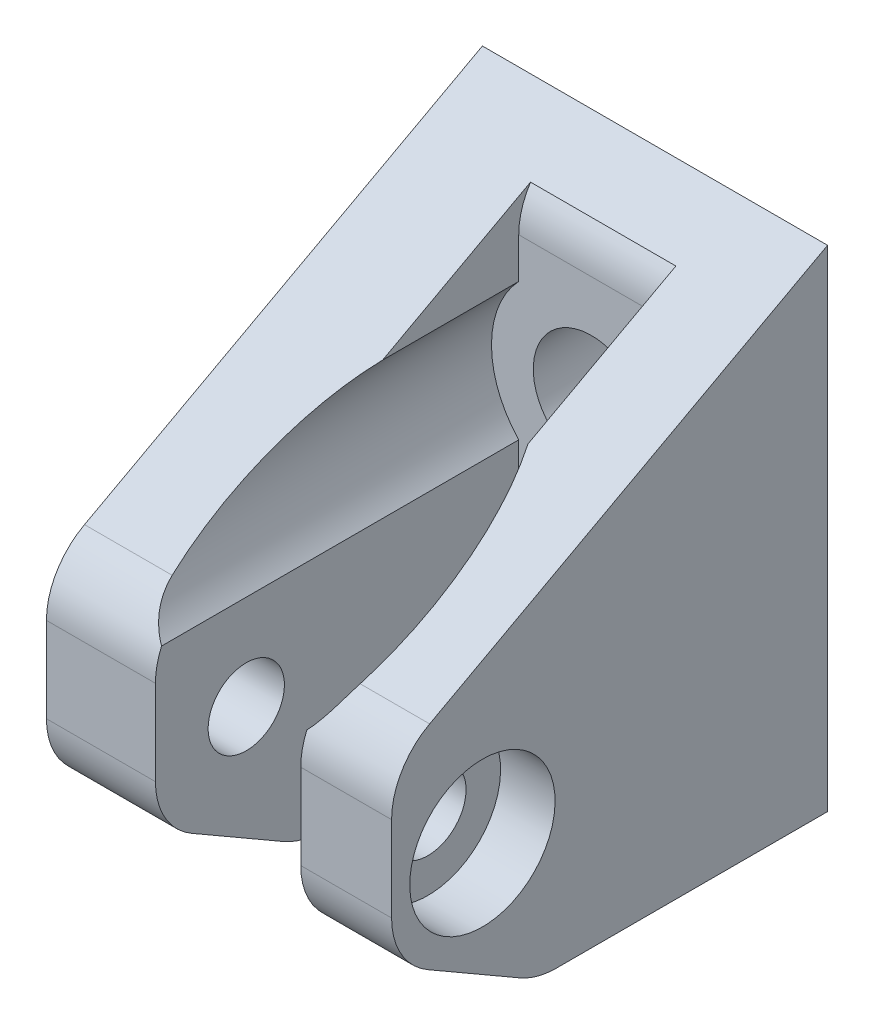
SolidWorks part; units mm, degrees
ref_plane "Plan de face" through (0, 0, 0) normal (0, 0, 1) x (1, 0, 0)
ref_plane "Plan de dessus" through (0, 0, 0) normal (0, 1, 0) x (1, 0, 0)
ref_plane "Plan de droite" through (0, 0, 0) normal (1, 0, 0) x (0, 0, -1)
sketch "Esquisse1" plane through (0, 0, 0) normal (0, 0, 1) x (1, 0, 0)
  line L1 (-10, 17) -> (10, 17)
  line L2 (-10, 17) -> (-10, -17)
  line L3 (-10, -17) -> (10, -17)
  line L4 (10, 17) -> (10, -17)
  dimension "D1" = 34
  dimension "D2" = 10
  dimension "D3" = 20
  dimension "D4" = 17
extrude "Boss.-Extru.1" add sketch "Esquisse1" along normal blind 4
sketch "Esquisse2" plane through (0, 0, 4) normal (0, 0, 1) x (1, 0, 0)
  line L0 (10, 17) -> (-10, 17) construction
  line L1 (-4, 17) -> (4, 17)
  line L2 (-4, 17) -> (-4, 10)
  line L3 (-4, 10) -> (4, 10)
  line L4 (4, 17) -> (4, 10)
  line L5 (10, -17) -> (10, 17) construction
  line L6 (-4, -17) -> (4, -17)
  line L7 (-4, -17) -> (-4, -10)
  line L8 (-4, -10) -> (4, -10)
  line L9 (4, -17) -> (4, -10)
  line L10 (-10, -17) -> (10, -17) construction
  dimension "D1" = 8
  dimension "D2" = 6
  dimension "D3" = 6
  dimension "D4" = 8
  dimension "D5" = 20
extrude "Enlèv. mat.-Extru.1" cut sketch "Esquisse2" against normal through all
fillet "Congé1" radius 4 2 edges at (0, -10, 4) (0, 10, 4)
sketch "Esquisse3" plane through (0, 0, 4) normal (0, 0, 1) x (1, 0, 0)
  line L1 (-10, 17) -> (-4, 17)
  line L2 (-10, 17) -> (-10, -17)
  line L3 (-10, -17) -> (-4, -17)
  line L4 (-4, 17) -> (-4, -17)
  line L5 (4, -17) -> (10, -17)
  line L6 (4, -17) -> (4, 17)
  line L7 (4, 17) -> (10, 17)
  line L8 (10, -17) -> (10, 17)
extrude "Boss.-Extru.2" add sketch "Esquisse3" along normal blind 20
sketch "Esquisse4" plane through (10, 0, 0) normal (1, 0, 0) x (0, 0, -1)
  line L0 (-24, -17) -> (0, -17) construction
  line L3 (-24, -17) -> (-24, 17) construction
  circle A0 centre (-19, 9) radius 2.1
  circle A1 centre (-19, -9) radius 2.1
  dimension "D1" = 4.2
  dimension "D2" = 4.2
  dimension "D3" = 18
  dimension "D4" = 8
  dimension "D5" = 5
  dimension "D6" = 5
extrude "Enlèv. mat.-Extru.2" cut sketch "Esquisse4" against normal through all
chamfer "Chanfrein1" distance 8 angle 30 4 edges at (-7, -17, 24) (7, -17, 24) (-7, 17, 24) (7, 17, 24) first distance on face at (-7, -17, 12) first distance on face at (7, -17, 12) first distance on face at (-7, 17, 12) first distance on face at (7, 17, 12)
fillet "Congé2" radius 4 8 edges at (7, 17, 16) (-7, 17, 16) (-7, 12.3812, 24) (7, 12.3812, 24) (7, -12.3812, 24) (7, -17, 16) (-7, -17, 16) (-7, -12.3812, 24)
sketch "Esquisse5" plane through (0, 0, 4) normal (0, 0, 1) x (1, 0, 0)
  circle A0 centre (0, 0) radius 3.2
  dimension "D1" = 6.4
extrude "Enlèv. mat.-Extru.3" cut sketch "Esquisse5" against normal through all
sketch "Esquisse6" plane through (0, 0, 4) normal (0, 0, 1) x (1, 0, 0)
  circle A0 centre (0, 0) radius 5.5
  dimension "D1" = 11
extrude "Enlèv. mat.-Extru.4" cut sketch "Esquisse6" along normal through all
sketch "Esquisse8" plane through (10, 0, 0) normal (1, 0, 0) x (0, 0, -1)
  line L0 (0, 17) -> (0, 10)
  line L1 (0, -17) -> (0, 17) construction
  line L2 (0, 10) -> (-24, -3)
  line L3 (-24, -10.0718) -> (-24, 10.0718) construction
  line L4 (-24, -3) -> (-24, 17)
  line L5 (-24, 17) -> (0, 17)
  dimension "D1" = 20
extrude "Enlèv. mat.-Extru.5" cut sketch "Esquisse8" against normal through all
fillet "Congé3" radius 4 2 edges at (7.3049, -3, 24) (-7.3049, -3, 24)
sketch "Esquisse9" plane through (10, 0, 0) normal (1, 0, 0) x (0, 0, -1)
  line L1 (3.8248, 14.6988) -> (-26.7691, 14.6988)
  line L2 (3.8248, 14.6988) -> (3.8248, -18.2977)
  line L3 (3.8248, -18.2977) -> (-26.7691, -18.2977)
  line L4 (-26.7691, 14.6988) -> (-26.7691, -18.2977)
extrude "Enlèv. mat.-Extru.6" cut sketch "Esquisse9" against normal blind 1
sketch "Esquisse10" plane through (9, 0, 0) normal (1, 0, 0) x (0, 0, -1)
  circle A0 centre (-19, -9) radius 4
  dimension "D1" = 8
extrude "Enlèv. mat.-Extru.7" cut sketch "Esquisse10" against normal blind 3
